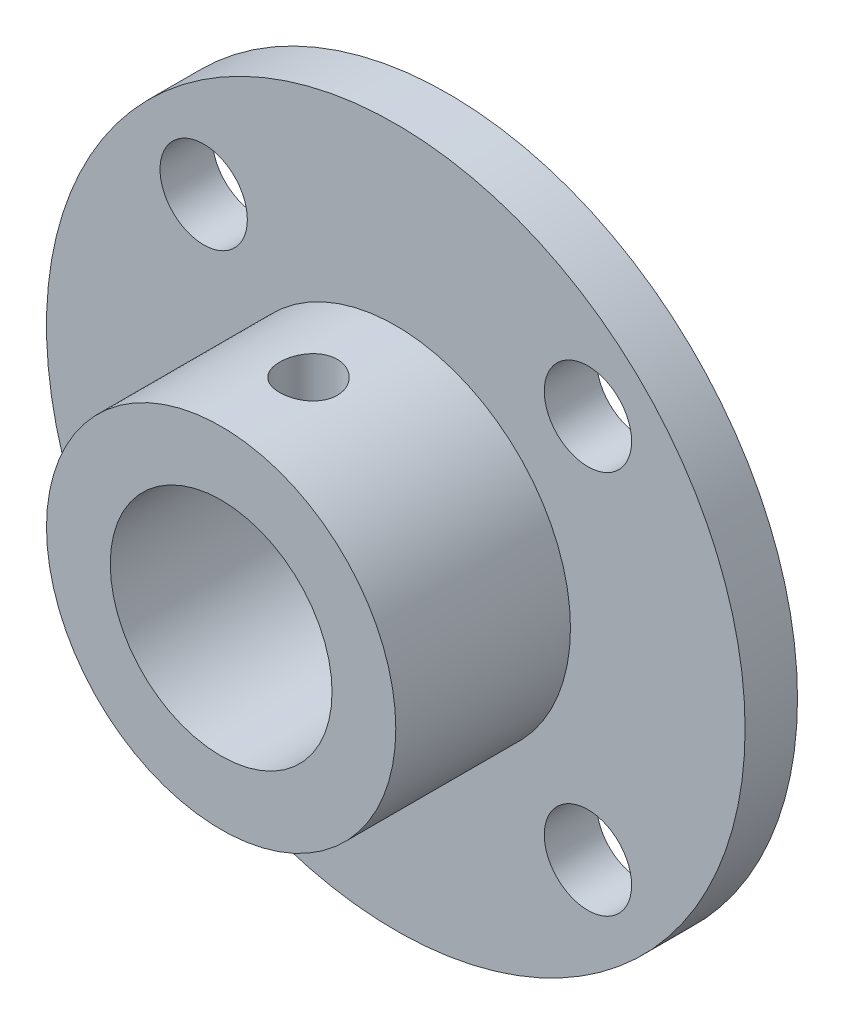
SolidWorks part; units mm, degrees
ref_plane "Front Plane" through (0, 0, 0) normal (0, 0, 1) x (1, 0, 0)
ref_plane "Top Plane" through (0, 0, 0) normal (0, 1, 0) x (1, 0, 0)
ref_plane "Right Plane" through (0, 0, 0) normal (1, 0, 0) x (0, 0, -1)
sketch "Sketch1" plane through (0, 0, 0) normal (0, 0, 1) x (1, 0, 0)
  circle A0 centre (0, 0) radius 20
  dimension "D1" = 40
extrude "Boss-Extrude1" add sketch "Sketch1" along normal blind 3
sketch "Sketch2" plane through (0, 0, 3) normal (0, 0, 1) x (1, 0, 0)
  circle A0 centre (0, 0) radius 10
  dimension "D1" = 20
extrude "Boss-Extrude2" add sketch "Sketch2" along normal blind 10
sketch "Sketch4" plane through (0, 0, 13) normal (0, 0, 1) x (1, 0, 0)
  circle A0 centre (0, 0) radius 6.35
  dimension "D1" = 12.7
extrude "Cut-Extrude1" cut sketch "Sketch4" against normal through all
ref_plane "Plane2" through (0, 0, 8) normal (0, 0, 1) x (1, 0, 0)
hole_wizard "M4 Tapped Hole1" positions "3DSketch7" profile "Sketch15" tap size "M4" standard "ISO" end condition up to next
sketch3d "3DSketch7"
  point P0 (0, 10, 8)
sketch "Sketch15" plane through (0, 10, 8) normal (1, 0, 0) x (0, 0, 1)
  line L0 (0, 0) -> (0, 3.65)
  line L1 (0, 3.65) -> (1.65, 3.65)
  line L2 (1.65, 3.65) -> (1.65, 0)
  line L5 (1.65, 0) -> (0, 0)
  line L11 (0, -6.35) -> (0, 107.95) construction
  dimension "Thru Tap Drill Dia." = 3.3
  dimension "Thru Tap Drill Depth" = 3.65
cosmetic thread "Hole Thread1" parameters "D2"=4
sketch "Sketch16" plane through (0, 0, 3) normal (0, 0, 1) x (1, 0, 0)
  line L0 (0, 0) -> (34.2865, 0) construction
  line L1 (0, 0) -> (11, 11) construction
  point P0 (11, 11)
  dimension "D1" = 11
  dimension "D2" = 45
hole_wizard "Ø5.0 (5) Diameter Hole1" positions "3DSketch8" profile "Sketch17" hole size "Ø5.0" standard "ISO" end condition through all
sketch3d "3DSketch8"
  point P0 (11, 11, 3)
sketch "Sketch17" plane through (11, 11, 3) normal (1, 0, 0) x (0, -1, 0)
  line L0 (0, 0) -> (0, 3)
  line L1 (0, 3) -> (2.5, 3)
  line L2 (2.5, 3) -> (2.5, 0)
  line L5 (2.5, 0) -> (0, 0)
  line L11 (0, -6.35) -> (0, 107.95) construction
  dimension "Thru Hole Dia." = 5
  dimension "Thru Hole Depth" = 3
pattern_circular "CirPattern1" count 4 over 360 about axis through (0, 0, 13) along (0, 0, -1) of "Ø5.0 (5) Diameter Hole1"
